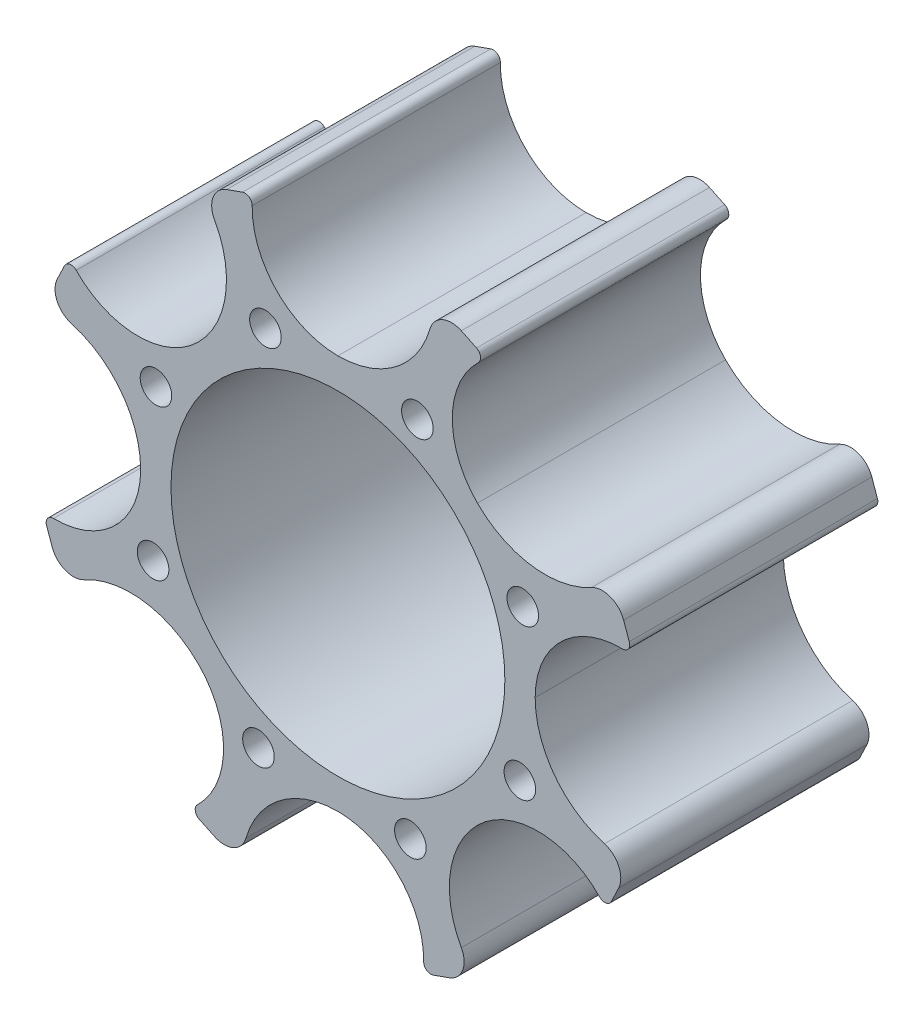
SolidWorks part; units mm, degrees
material "ABS"
ref_plane "前视基准面" through (0, 0, 0) normal (0, 0, 1) x (1, 0, 0)
ref_plane "上视基准面" through (0, 0, 0) normal (0, 1, 0) x (1, 0, 0)
ref_plane "右视基准面" through (0, 0, 0) normal (1, 0, 0) x (0, 0, -1)
sketch "草图1" plane through (0, 0, 0) normal (0, 0, 1) x (1, 0, 0)
  line L0 (0, 31.3575) -> (0, 0) construction
  line L1 (0, 0) -> (22.1731, 22.1731) construction
  line L4 (0, 31.3575) -> (22.1731, 22.1731) construction
  line L6 (11.6409, 26.5357) -> (12.5976, 28.8454) construction
  line L7 (21.7656, 23.184) -> (15.5687, 29.0018) construction
  line L8 (21.7656, 23.184) -> (27.9942, 29.8184) construction
  line L9 (15.357, 30.2989) -> (13.674, 31.1018)
  line L10 (32.2836, 10.5656) -> (31.6613, 12.3233)
  line L11 (30.2989, -15.357) -> (31.1018, -13.674)
  line L12 (10.5656, -32.2836) -> (12.3233, -31.6613)
  line L13 (-15.357, -30.2989) -> (-13.674, -31.1018)
  line L14 (-32.2836, -10.5656) -> (-31.6613, -12.3233)
  line L15 (-30.2989, 15.357) -> (-31.1018, 13.674)
  line L16 (-10.5656, 32.2836) -> (-12.3233, 31.6613)
  circle A0 centre (0, 0) radius 31.3575 construction
  arc A9 (15.5687, 29.0018) -> (15.4556, 15.4556) centre (22.1731, 22.1731) ccw
  circle A13 centre (0, 0) radius 40.9 construction
  arc A16 (15.5687, 29.0018) -> (15.357, 30.2989) centre (15.0125, 29.5769) ccw
  arc A17 (13.674, 31.1018) -> (10.1948, 29.5357) centre (12.5976, 28.8454) ccw
  arc A18 (0, 21.8575) -> (10.1948, 29.5357) centre (0, 32.4647) ccw
  arc A19 (31.5161, 9.4987) -> (21.8575, 0) centre (31.3575, 0) ccw
  arc A20 (31.5161, 9.4987) -> (32.2836, 10.5656) centre (31.5295, 10.2986) ccw
  arc A21 (31.6613, 12.3233) -> (28.0937, 13.6761) centre (29.3046, 11.4889) ccw
  arc A22 (15.4556, 15.4556) -> (28.0937, 13.6761) centre (22.956, 22.956) ccw
  arc A24 (29.0018, -15.5687) -> (15.4556, -15.4556) centre (22.1731, -22.1731) ccw
  arc A25 (29.0018, -15.5687) -> (30.2989, -15.357) centre (29.5769, -15.0125) ccw
  arc A26 (31.1018, -13.674) -> (29.5357, -10.1948) centre (28.8454, -12.5976) ccw
  arc A27 (21.8575, 0) -> (29.5357, -10.1948) centre (32.4647, 0) ccw
  arc A29 (9.4987, -31.5161) -> (0, -21.8575) centre (0, -31.3575) ccw
  arc A30 (9.4987, -31.5161) -> (10.5656, -32.2836) centre (10.2986, -31.5295) ccw
  arc A31 (12.3233, -31.6613) -> (13.6761, -28.0937) centre (11.4889, -29.3046) ccw
  arc A32 (15.4556, -15.4556) -> (13.6761, -28.0937) centre (22.956, -22.956) ccw
  arc A34 (-15.5687, -29.0018) -> (-15.4556, -15.4556) centre (-22.1731, -22.1731) ccw
  arc A35 (-15.5687, -29.0018) -> (-15.357, -30.2989) centre (-15.0125, -29.5769) ccw
  arc A36 (-13.674, -31.1018) -> (-10.1948, -29.5357) centre (-12.5976, -28.8454) ccw
  arc A37 (0, -21.8575) -> (-10.1948, -29.5357) centre (0, -32.4647) ccw
  arc A39 (-31.5161, -9.4987) -> (-21.8575, 0) centre (-31.3575, 0) ccw
  arc A40 (-31.5161, -9.4987) -> (-32.2836, -10.5656) centre (-31.5295, -10.2986) ccw
  arc A41 (-31.6613, -12.3233) -> (-28.0937, -13.6761) centre (-29.3046, -11.4889) ccw
  arc A42 (-15.4556, -15.4556) -> (-28.0937, -13.6761) centre (-22.956, -22.956) ccw
  arc A44 (-29.0018, 15.5687) -> (-15.4556, 15.4556) centre (-22.1731, 22.1731) ccw
  arc A45 (-29.0018, 15.5687) -> (-30.2989, 15.357) centre (-29.5769, 15.0125) ccw
  arc A46 (-31.1018, 13.674) -> (-29.5357, 10.1948) centre (-28.8454, 12.5976) ccw
  arc A47 (-21.8575, 0) -> (-29.5357, 10.1948) centre (-32.4647, 0) ccw
  arc A49 (-9.4987, 31.5161) -> (0, 21.8575) centre (0, 31.3575) ccw
  arc A50 (-9.4987, 31.5161) -> (-10.5656, 32.2836) centre (-10.2986, 31.5295) ccw
  arc A51 (-12.3233, 31.6613) -> (-13.6761, 28.0937) centre (-11.4889, 29.3046) ccw
  arc A52 (-15.4556, 15.4556) -> (-13.6761, 28.0937) centre (-22.956, 22.956) ccw
  point P98 (0, 0)
  dimension "D1" = 9.5
  dimension "D3" = 45
  dimension "D5" = 9.1
  dimension "D8" = 81.8
  dimension "D9" = 9.5
  dimension "D10" = 2.5
  dimension "D11" = 0.8
  dimension "D2" = 24
  dimension "D6" = 11.4
  dimension "D7" = 2.5
  dimension "D13" = 8.5
  dimension "D12" = 8
extrude "凸台-拉伸1" add sketch "草图1" along normal blind 27.5
sketch "草图2" plane through (0, 0, 0) normal (0, 0, -1) x (-1, 0, 0)
  line L0 (0, 0) -> (21.8575, 0) construction
  line L1 (0, 0) -> (15.4556, -15.4556) construction
  arc A0 (20.6575, 0) -> (24.8509, -8.4944) centre (31.3575, 0) ccw construction
  arc A1 (23.828, -11.1811) -> (14.6071, -14.6071) centre (22.956, -22.956) ccw construction
  arc A2 (23.828, -11.1811) -> (24.8509, -8.4944) centre (23.9388, -9.6852) ccw construction
  circle A3 centre (0, 0) radius 18.5
  arc A4 (28.0937, -13.6761) -> (15.4556, -15.4556) centre (22.956, -22.956) ccw construction
  arc A5 (21.8575, 0) -> (31.5161, -9.4987) centre (31.3575, 0) ccw construction
  arc A6 (14.6071, -14.6071) -> (11.5658, -23.5787) centre (22.1731, -22.1731) ccw construction
  arc A7 (8.9427, -24.7551) -> (0, -20.6575) centre (0, -32.4647) ccw construction
  arc A8 (8.9427, -24.7551) -> (11.5658, -23.5787) centre (10.0788, -23.7757) ccw construction
  arc A9 (0, -20.6575) -> (-8.4944, -24.8509) centre (0, -31.3575) ccw construction
  arc A10 (-11.1811, -23.828) -> (-14.6071, -14.6071) centre (-22.956, -22.956) ccw construction
  arc A11 (-11.1811, -23.828) -> (-8.4944, -24.8509) centre (-9.6852, -23.9388) ccw construction
  arc A12 (-14.6071, -14.6071) -> (-23.5787, -11.5658) centre (-22.1731, -22.1731) ccw construction
  arc A13 (-24.7551, -8.9427) -> (-20.6575, 0) centre (-32.4647, 0) ccw construction
  arc A14 (-24.7551, -8.9427) -> (-23.5787, -11.5658) centre (-23.7757, -10.0788) ccw construction
  arc A15 (-20.6575, 0) -> (-24.8509, 8.4944) centre (-31.3575, 0) ccw construction
  arc A16 (-23.828, 11.1811) -> (-14.6071, 14.6071) centre (-22.956, 22.956) ccw construction
  arc A17 (-23.828, 11.1811) -> (-24.8509, 8.4944) centre (-23.9388, 9.6852) ccw construction
  arc A18 (-14.6071, 14.6071) -> (-11.5658, 23.5787) centre (-22.1731, 22.1731) ccw construction
  arc A19 (-8.9427, 24.7551) -> (0, 20.6575) centre (0, 32.4647) ccw construction
  arc A20 (-8.9427, 24.7551) -> (-11.5658, 23.5787) centre (-10.0788, 23.7757) ccw construction
  arc A21 (0, 20.6575) -> (8.4944, 24.8509) centre (0, 31.3575) ccw construction
  arc A22 (11.1811, 23.828) -> (14.6071, 14.6071) centre (22.956, 22.956) ccw construction
  arc A23 (11.1811, 23.828) -> (8.4944, 24.8509) centre (9.6852, 23.9388) ccw construction
  arc A24 (14.6071, 14.6071) -> (23.5787, 11.5658) centre (22.1731, 22.1731) ccw construction
  arc A25 (24.7551, 8.9427) -> (20.6575, 0) centre (32.4647, 0) ccw construction
  arc A26 (24.7551, 8.9427) -> (23.5787, 11.5658) centre (23.7757, 10.0788) ccw construction
  point P72 (0, 0)
  dimension "D1" = 1.2
  dimension "D2" = 1.2
  dimension "D3" = 1.5
  dimension "D5" = 37
  dimension "D4" = 8
extrude "切除-拉伸1" cut sketch "草图2" against normal through all
sketch "草图3" plane through (0, 0, 0) normal (0, 0, -1) x (-1, 0, 0)
  line L0 (-12.5976, 28.8454) -> (0, 0) construction
  circle A0 centre (0, 0) radius 22 construction
  circle A1 centre (-8.8049, 20.1612) radius 1.75
  dimension "D1" = 44
  dimension "D2" = 3.5
extrude "切除-拉伸2" cut sketch "草图3" against normal through all
sketch "草图4" plane through (0, 0, 0) normal (0, 0, -1) x (-1, 0, 0)
  line L0 (-10.0989, 23.1241) -> (0, 0) construction
  line L1 (-10.0989, 23.1241) -> (-12.0179, 20.522)
  line L2 (-12.0179, 20.522) -> (-10.7239, 17.5591)
  line L3 (-10.7239, 17.5591) -> (-7.511, 17.1982)
  line L4 (-7.511, 17.1982) -> (-5.592, 19.8003)
  line L5 (-5.592, 19.8003) -> (-6.886, 22.7633)
  line L6 (-6.886, 22.7633) -> (-10.0989, 23.1241)
  circle A0 centre (-8.8049, 20.1612) radius 2.8 construction
  dimension "D1" = 5.6
extrude "切除-拉伸3" cut sketch "草图4" against normal blind 5
pattern_circular "阵列(圆周)1" count 8 over 360 about axis through (0, 0, 27.5) along (0, 0, -1) of "切除-拉伸2", "切除-拉伸3" reverse direction yes
